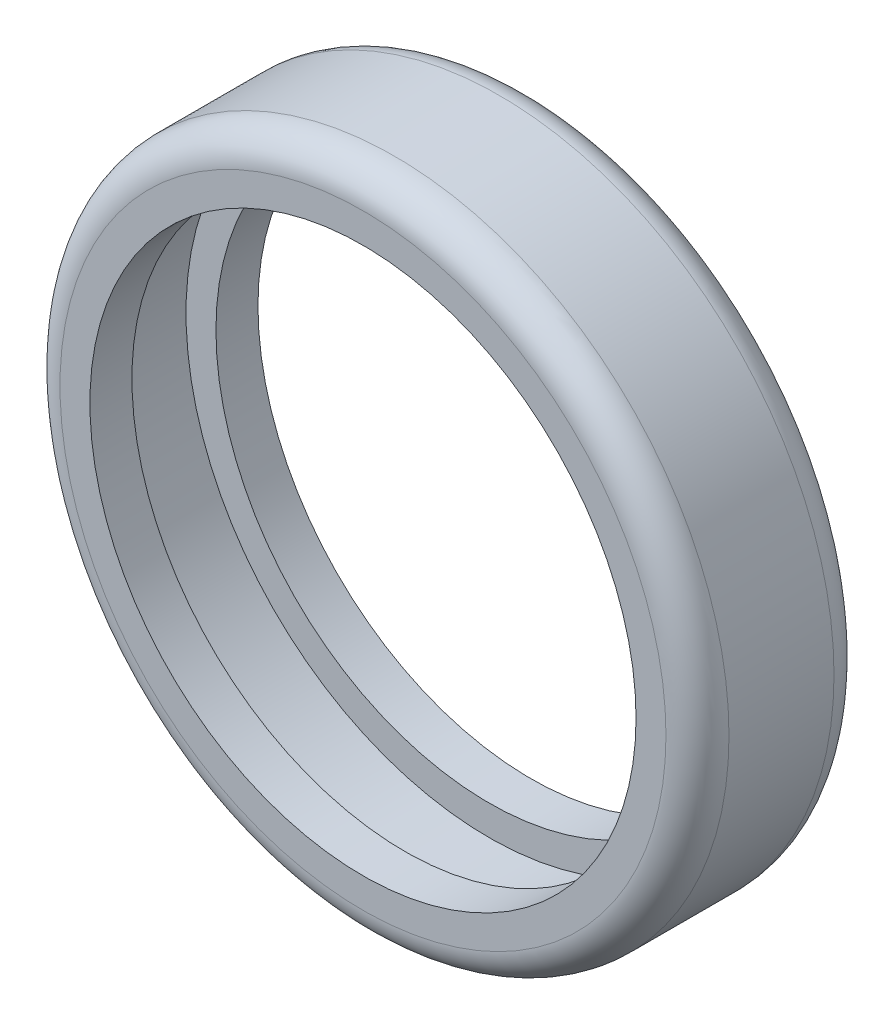
SolidWorks part; units mm, degrees
ref_plane "Plan de face" through (0, 0, 0) normal (0, 0, 1) x (1, 0, 0)
ref_plane "Plan de dessus" through (0, 0, 0) normal (0, 1, 0) x (1, 0, 0)
ref_plane "Plan de droite" through (0, 0, 0) normal (1, 0, 0) x (0, 0, -1)
sketch "Esquisse1" plane through (0, 0, 0) normal (0, 0, 1) x (1, 0, 0)
  circle A0 centre (0, 0) radius 28.85
  circle A1 centre (0, 0) radius 31.85
extrude "Boss.-Extru.1" add sketch "Esquisse1" along normal blind 8 contours A1 A0 region at (-30.9491, 0, 0)
sketch "Esquisse2" plane through (0, 0, 8) normal (0, 0, 1) x (1, 0, 0)
  circle A0 centre (0, 0) radius 26
  circle A1 centre (0, 0) radius 31.85
extrude "Boss.-Extru.2" add sketch "Esquisse2" along normal blind 4
sketch "Esquisse3" plane through (0, 0, 0) normal (0, 0, -1) x (-1, 0, 0)
  circle A0 centre (0, 0) radius 31.85
  circle A3 centre (0, 0) radius 26
extrude "Boss.-Extru.3" add sketch "Esquisse3" along normal blind 4
fillet "Congé1" radius 3 2 edges at (31.85, 0, 12) (-31.85, 0, -4)
